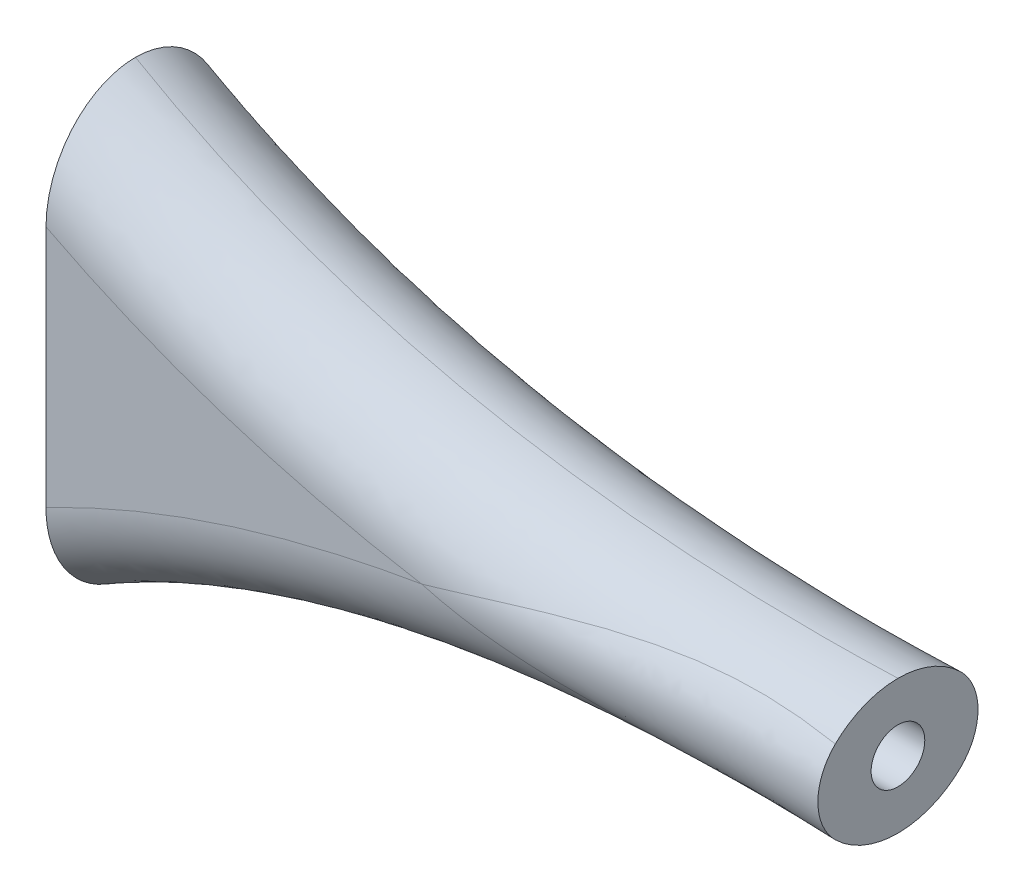
SolidWorks part; units mm, degrees
material "Natural Rubber"
ref_plane "Front Plane" through (0, 0, 0) normal (0, 0, 1) x (1, 0, 0)
ref_plane "Top Plane" through (0, 0, 0) normal (0, 1, 0) x (1, 0, 0)
ref_plane "Right Plane" through (0, 0, 0) normal (1, 0, 0) x (0, 0, -1)
sketch "Sketch3" plane through (0, 0, 0) normal (0, 0, 1) x (1, 0, 0)
  line L0 (0, -50) -> (0, 50)
  line L1 (0, 0) -> (170.5, 0) construction
  line L2 (170.5, -15) -> (170.5, 15)
  spline S0 degree 3 poles (0, 50) (51.1136, 20.1851) (112.3284, 12.9331) (170.5, 15) knots 0 0 0 0 1 1 1 1
  spline S1 degree 3 poles (0, -50) (51.1136, -20.1851) (112.3284, -12.9331) (170.5, -15) knots 0 0 0 0 1 1 1 1
  dimension "D1" = 50
  dimension "D2" = 15
  dimension "D3" = 30.695
  dimension "D4" = 22.5754
  dimension "D5" = 42.8421
  dimension "D6" = 98.0749
  dimension "D7" = 170.5
extrude "Boss-Extrude1" add sketch "Sketch3" along normal mid plane 40
fillet "Fillet1" radius 20 4 edges
fillet "Fillet2" radius 13 1 edges at (83.9939, 0, 20)
fillet "Fillet3" radius 13 1 edges at (83.9892, 0, -20)
sketch "Sketch4" plane through (170.5, 0, 0) normal (1, 0, 0) x (0, 0, -1)
  circle A0 centre (0, 0) radius 6
  dimension "D1" = 12
extrude "Cut-Extrude1" cut sketch "Sketch4" against normal blind 20
sketch "Sketch5" plane through (0, 0, 0) normal (-1, 0, 0) x (0, 0, 1)
  circle A0 centre (0, 0) radius 15
  dimension "D1" = 30
extrude "Cut-Extrude2" cut sketch "Sketch5" against normal blind 20
